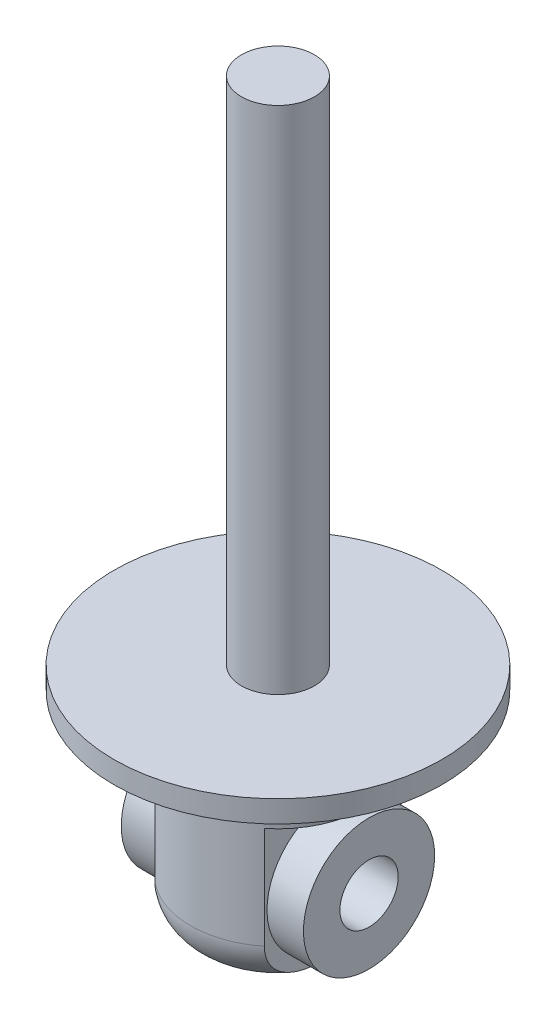
SolidWorks part; units mm, degrees
ref_plane "Front Plane" through (0, 0, 0) normal (0, 0, 1) x (1, 0, 0)
ref_plane "Top Plane" through (0, 0, 0) normal (0, 1, 0) x (1, 0, 0)
ref_plane "Right Plane" through (0, 0, 0) normal (1, 0, 0) x (0, 0, -1)
sketch "Sketch1" plane through (0, 0, 0) normal (0, 1, 0) x (1, 0, 0)
  circle A0 centre (0, 0) radius 22.5
extrude "Boss-Extrude1" add sketch "Sketch1" along normal blind 3
sketch "Sketch2" plane through (0, 3, 0) normal (0, 1, 0) x (1, 0, 0)
  circle A0 centre (0, 0) radius 5
extrude "Boss-Extrude2" add sketch "Sketch2" along normal blind 70
sketch "Sketch3" plane through (0, 0, 0) normal (0, -1, 0) x (1, 0, 0)
  circle A0 centre (0, 0) radius 12
extrude "Boss-Extrude3" add sketch "Sketch3" along normal blind 28
fillet "Fillet1" radius 6 1 edges at (0, -28, -12)
sketch "Sketch4" plane through (0, 0, 0) normal (0, 0, 1) x (1, 0, 0)
  line L0 (0, 0) -> (0, -28) construction
  line L1 (-6, -28) -> (6, -28) construction
  line L2 (7.5, -28) -> (27.5, -28)
  line L3 (27.5, -28) -> (27.5, -8)
  line L4 (27.5, -8) -> (7.5, -8)
  line L5 (7.5, -8) -> (7.5, -28)
  line L6 (-7.5, -8) -> (-7.5, -28)
  line L7 (-27.5, -8) -> (-7.5, -8)
  line L8 (-27.5, -28) -> (-27.5, -8)
  line L9 (-7.5, -28) -> (-27.5, -28)
  dimension "D1" = 20
  dimension "D2" = 15
  dimension "D3" = 20
extrude "Cut-Extrude1" cut sketch "Sketch4" against normal blind 28 and the other way blind 28
sketch "Sketch5" plane through (7.5, 0, 0) normal (1, 0, 0) x (0, 0, -1)
  line L0 (0, -8) -> (0, -27.8095) construction
  line L2 (-9.3675, -8) -> (9.3675, -8) construction
  circle A1 centre (0, -17.9047) radius 4
  spline S0 degree 3 poles (9.3675, -22) (9.3675, -22.256) (9.346, -22.5161) (9.2617, -23.0236) (9.1993, -23.2718) (9.0353, -23.7573) (8.9325, -23.9966) (8.6933, -24.4529) (8.5573, -24.67) (8.2544, -25.0836) (8.0864, -25.2813) (7.7261, -25.6506) (7.5349, -25.8216) (6.9312, -26.2977) (6.4844, -26.5672) (5.5607, -27.0045) (5.0803, -27.1758) (4.0917, -27.4469) (3.5846, -27.5457) (2.5722, -27.6899) (2.0636, -27.7363) (1.0432, -27.7958) (0.5315, -27.8091) (-0.4943, -27.8098) (-1.0101, -27.797) (-2.0342, -27.7387) (-2.5445, -27.6929) (-3.56, -27.5501) (-4.0672, -27.4524) (-5.0646, -27.1812) (-5.5488, -27.0094) (-6.4792, -26.5703) (-6.9277, -26.3001) (-7.5323, -25.8239) (-7.7237, -25.6529) (-8.0841, -25.2839) (-8.2538, -25.0844) (-8.7096, -24.462) (-8.9491, -24.0109) (-9.1993, -23.2725) (-9.2623, -23.0206) (-9.3462, -22.5143) (-9.3675, -22.2585) (-9.3675, -22) knots 0 0 0 0 0.03125 0.03125 0.0625 0.0625 0.09375 0.09375 0.125 0.125 0.15625 0.15625 0.1875 0.1875 0.25 0.25 0.3125 0.3125 0.375 0.375 0.4375 0.4375 0.5 0.5 0.5625 0.5625 0.625 0.625 0.6875 0.6875 0.75 0.75 0.8125 0.8125 0.84375 0.84375 0.875 0.875 0.9375 0.9375 0.96875 0.96875 1 1 1 1 construction
extrude "Cut-Extrude2" cut sketch "Sketch5" against normal through all
sketch "Sketch6" plane through (0, 0, 0) normal (1, 0, 0) x (0, 0, -1)
  circle A1 centre (0, -17.9047) radius 9
  circle A2 centre (0, -17.9047) radius 4 construction
  circle A3 centre (0, -17.9047) radius 4
extrude "Boss-Extrude4" add sketch "Sketch6" along normal mid plane 25
